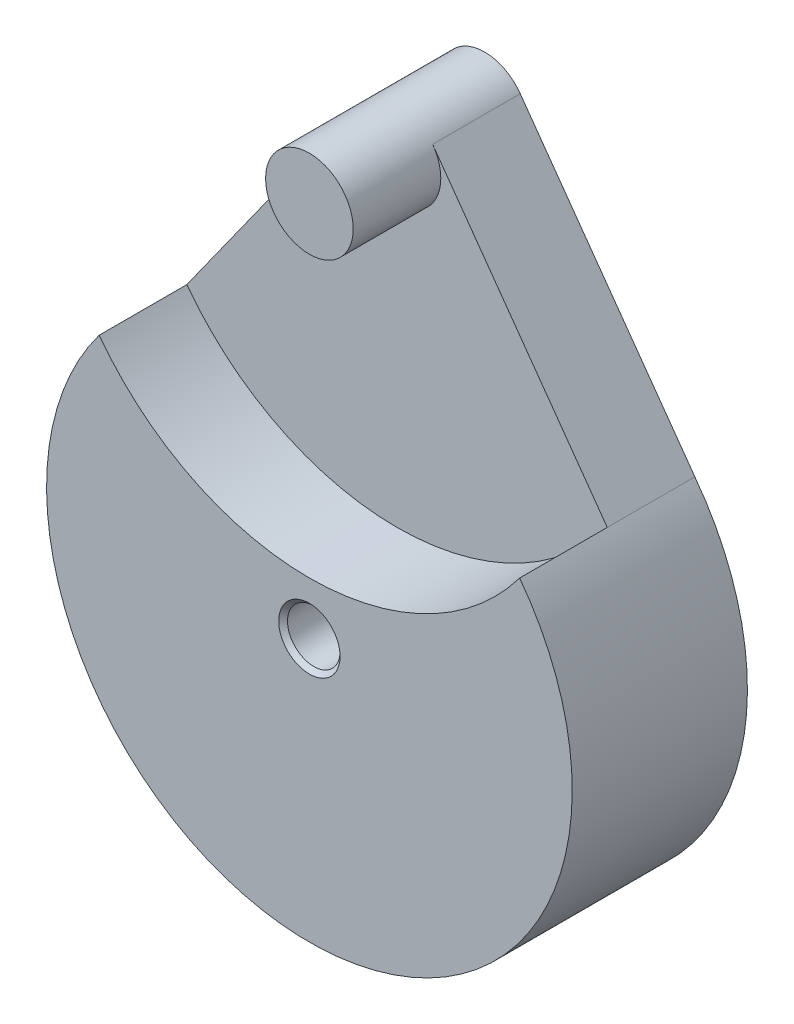
SolidWorks part; units mm, degrees
ref_plane "Ön Düzlem" through (0, 0, 0) normal (0, 0, 1) x (1, 0, 0)
ref_plane "Üst Düzlem" through (0, 0, 0) normal (0, 1, 0) x (1, 0, 0)
ref_plane "Sağ Düzlem" through (0, 0, 0) normal (1, 0, 0) x (0, 0, -1)
sketch "Sketch1" plane through (0, 0, 0) normal (0, 0, 1) x (1, 0, 0)
  circle A0 centre (0, 0) radius 50
  dimension "D1" = 100
extrude "Boss-Extrude1" add sketch "Sketch1" along normal blind 10
sketch "Sketch2" plane through (0, 0, 10) normal (0, 0, 1) x (1, 0, 0)
  line L0 (0, -69.7394) -> (0, 89.119) construction
  line L1 (-85.1612, 0) -> (85.98, 0) construction
  circle A0 centre (0, 43) radius 5
  arc A1 (-24, 18) -> (24, 18) centre (0, 0) ccw
  arc A2 (-24, 18) -> (24, 18) centre (0, 36) ccw
  dimension "D1" = 10
  dimension "D3" = 60
  dimension "D4" = 60
  dimension "D2" = 43
  dimension "D5" = 36
extrude "Boss-Extrude2" add sketch "Sketch2" along normal blind 10
sketch "Sketch3" plane through (0, 0, 20) normal (0, 0, 1) x (1, 0, 0)
  circle A0 centre (0, 0) radius 3
  dimension "D1" = 6
extrude "Cut-Extrude1" cut sketch "Sketch3" against normal through all
sketch "Sketch4" plane through (0, 0, 10) normal (0, 0, 1) x (1, 0, 0)
  line L0 (-24, 18) -> (-4.0688, 45.906)
  line L1 (24, 18) -> (4.0688, 45.906)
  line L2 (4.0688, 45.906) -> (24, 18)
  circle A0 centre (0, 43) radius 5 construction
  circle A1 centre (0, 0) radius 50
  circle A2 centre (0, 0) radius 50
  circle A3 centre (0, 43) radius 5 construction
  arc M2 (24, 18) -> (-24, 18) centre (0, 0) cw
  circle M4 centre (0, 43) radius 5
  circle M5 centre (0, 0) radius 50
  dimension "D1" = 0
extrude "Cut-Extrude2" cut sketch "Sketch4" against normal blind 31 and the other way through all contours L1 L0 M5 M2 M4 region at (-48.5858, 0, 10)
chamfer "Chamfer1" distance 0.5 angle 45 2 edges at (3, 0, 0) (3, 0, 20)
